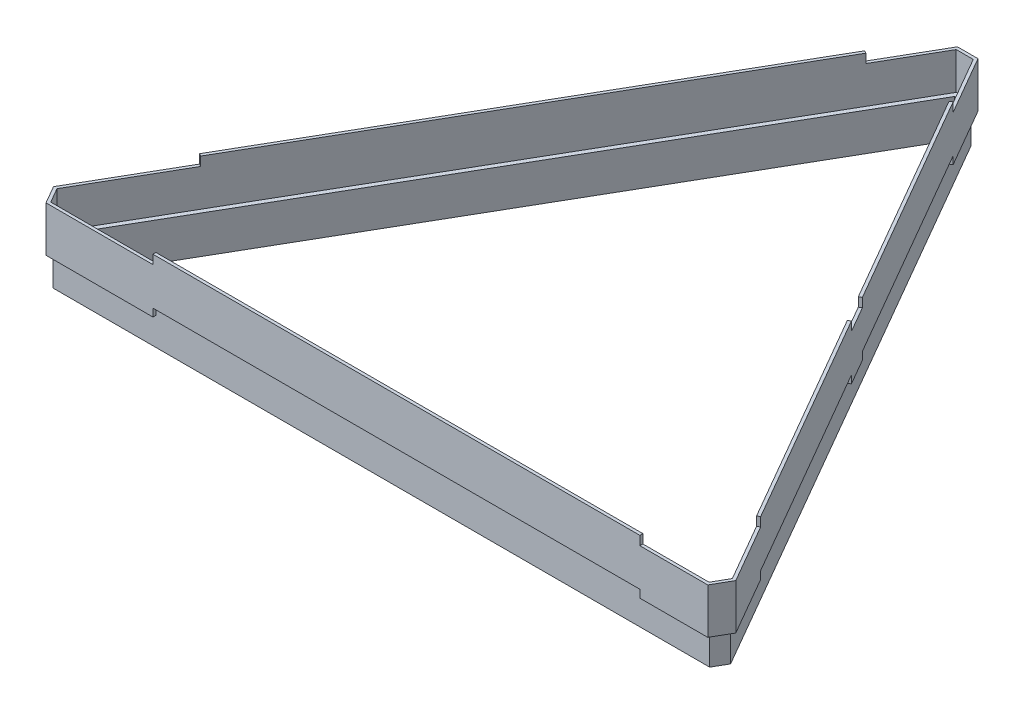
SolidWorks part; units mm, degrees
ref_plane "Front Plane" through (0, 0, 0) normal (0, 0, 1) x (1, 0, 0)
ref_plane "Top Plane" through (0, 0, 0) normal (0, 1, 0) x (1, 0, 0)
ref_plane "Right Plane" through (0, 0, 0) normal (1, 0, 0) x (0, 0, -1)
sketch "Sketch1" plane through (0, 0, 0) normal (0, 1, 0) x (1, 0, 0)
  line L17 (-4, 192.2576) -> (111, -6.9282) construction
  line L24 (4, 192.2576) -> (-111, -6.9282) construction
  line L25 (-115, 0) -> (115, 0) construction
  line L26 (-96.004, 30.9021) -> (-95.1379, 30.4021)
  line L27 (-111.2679, -2.4641) -> (-110.8349, -2.2141) construction
  line L28 (0, 192.2576) -> (0, 185.3294) construction
  line L29 (113, -3.4641) -> (107, 0) construction
  line L30 (59.5, 96.1288) -> (57.7679, 95.1288) construction
  line L31 (-59.5, 96.1288) -> (-57.7679, 95.1288) construction
  line L33 (-112.6906, 0) -> (-109.8453, -4.9282)
  line L36 (112.6906, 0) -> (109.8453, -4.9282)
  line L37 (-2.8453, 190.2576) -> (2.8453, 190.2576)
  line L46 (-74.74, -4.9282) -> (87.75, -4.9282)
  line L50 (-112.6906, 0) -> (-95.1379, 30.4021)
  line L51 (-13.8929, 171.1225) -> (-95.1379, 30.4021)
  line L52 (-14.759, 171.6225) -> (-13.8929, 171.1225)
  line L53 (-14.759, 171.6225) -> (-96.004, 30.9021)
  line L54 (13.8929, 171.1225) -> (14.759, 171.6225)
  line L55 (-109.8453, -4.9282) -> (-74.74, -4.9282)
  line L56 (109.8453, -4.9282) -> (87.75, -4.9282)
  line L57 (-74.74, -5.9282) -> (-74.74, -4.9282)
  line L58 (61.134, 91.2987) -> (56.134, 99.9589)
  line L59 (-2.8453, 190.2576) -> (-13.8929, 171.1225)
  line L60 (61.134, 91.2987) -> (102.509, 19.6351)
  line L61 (102.509, 19.6351) -> (113.8453, 0)
  line L62 (101.6429, 19.1351) -> (102.509, 19.6351)
  line L63 (101.6429, 19.1351) -> (112.6906, 0)
  line L64 (2.8453, 190.2576) -> (13.8929, 171.1225)
  line L65 (113.8453, 0) -> (110.4226, -5.9282)
  line L66 (56.134, 99.9589) -> (14.759, 171.6225)
  line L67 (55.2679, 99.4589) -> (13.8929, 171.1225)
  line L68 (0, -6.9282) -> (-74.74, -6.9282) construction
  line L69 (-14.759, 171.6225) -> (-3.4226, 191.2576)
  line L70 (-58.634, 95.6288) -> (-96.004, 30.9021) construction
  line L71 (-3.4226, 191.2576) -> (3.4226, 191.2576)
  line L72 (60.2679, 90.7987) -> (61.134, 91.2987)
  line L73 (55.2679, 99.4589) -> (56.134, 99.9589)
  line L74 (55.2679, 99.4589) -> (60.2679, 90.7987)
  line L75 (-74.74, -5.9282) -> (87.75, -5.9282)
  line L76 (60.2679, 90.7987) -> (101.6429, 19.1351)
  line L77 (57.7679, 95.1288) -> (57.3349, 94.8788) construction
  line L78 (57.3349, 94.8788) -> (-110.8349, -2.2141) construction
  line L79 (-110.8349, -2.2141) -> (-112.1132, 0)
  line L80 (-112.1132, 0) -> (-2.5566, 189.7576)
  line L81 (-2.5566, 189.7576) -> (2.5566, 189.7576)
  line L82 (2.5566, 189.7576) -> (112.1132, 0)
  line L83 (112.1132, 0) -> (109.5566, -4.4282)
  line L84 (109.5566, -4.4282) -> (-109.5566, -4.4282)
  line L85 (-109.5566, -4.4282) -> (-110.8349, -2.2141)
  line L86 (-57.3349, 94.8788) -> (-56.4689, 94.3788) construction
  line L93 (-56.4689, 94.3788) -> (-1.9793, 188.7576)
  line L94 (-1.9793, 188.7576) -> (1.9793, 188.7576)
  line L95 (1.9793, 188.7576) -> (110.9585, 0)
  line L96 (110.9585, 0) -> (108.9793, -3.4282)
  line L97 (108.9793, -3.4282) -> (-108.9793, -3.4282)
  line L98 (-108.9793, -3.4282) -> (-110.9585, 0)
  line L99 (-110.9585, 0) -> (-56.4689, 94.3788)
  line L100 (-111.2679, -2.4641) -> (-112.134, -2.9641) construction
  line L101 (-112.134, -2.9641) -> (-113.8453, 0)
  line L102 (-113.8453, 0) -> (-96.004, 30.9021)
  line L103 (-112.134, -2.9641) -> (-110.4226, -5.9282)
  line L104 (-110.4226, -5.9282) -> (-74.74, -5.9282)
  line L105 (3.4226, 191.2576) -> (14.759, 171.6225)
  line L106 (110.4226, -5.9282) -> (87.75, -5.9282)
  line L107 (87.75, -5.9282) -> (87.75, -4.9282)
  point P23 (-57.7679, 95.1288)
  point P28 (57.7679, 95.1288)
  point P29 (58.634, 95.6288)
  point P34 (-58.634, 95.6288)
  point P38 (14.759, 171.6225)
  point P41 (-14.759, 171.6225)
  point P44 (102.509, 19.6351)
  point P47 (-96.004, 30.9021)
  point P48 (59.5, 96.1288)
  point P62 (-54.7369, 93.3788)
  dimension "D1" = 8
  dimension "D2" = 8
  dimension "D3" = 8
  dimension "D4" = 230
  dimension "D5" = 230
  dimension "D6" = 230
  dimension "D7" = 74.74
  dimension "D8" = 2
extrude "Boss-Extrude1" add sketch "Sketch1" along normal blind 0.2 contours L59 L37 L64 | L76 L74 L67 L64 L37 L59 L51 L50 L33 L55 L46 L56 L36 L63 L84 L85 L79 L80 L81 L82 L83 | L67 | L74 | L76 | L63 L36 L56 | L46 | L55 L33 L50 | L51 | L85 L84 L83 L82 L81 L80 L79 region at (-54.9485, 0, -101.0123) region at (-95.8396, 0, -30.1869) region at (-54.2572, 0, -100.6132) region at (-8.7814, 0, -181.2614) region at (6.505, 0, 5.4282) region at (35.0135, 0, -135.5407) region at (98.7976, 0, 5.2935) region at (58.201, 0, -95.3788) region at (81.3885, 0, -55.2169) region at (-111.2172, 0, 0.9587)
extrude "Boss-Extrude2" add sketch "Sketch1<7>" along normal blind 12.58 contours L63 L36 L56 | L59 L37 L64 | L55 L33 L50 | L74 region at (-95.8396, 0, -30.1869) region at (-8.7814, 0, -181.2614) region at (98.7976, 0, 5.2935) region at (58.201, 0, -95.3788)
sketch "Sketch1<7>" plane through (0, 0, 0) normal (0, 1, 0) x (1, 0, 0) same geometry as "Sketch1"
extrude "Boss-Extrude3" add sketch "Sketch1<8>" along normal blind 15.58 contours L46 | L51 | L76 | L67 region at (-54.9485, 0, -101.0123) region at (6.505, 0, 5.4282) region at (35.0135, 0, -135.5407) region at (81.3885, 0, -55.2169)
sketch "Sketch1<8>" plane through (0, 0, 0) normal (0, 1, 0) x (1, 0, 0) same geometry as "Sketch1"
extrude "Boss-Extrude4" add sketch "Sketch1<9>" against normal blind 12.38 contours L85 L84 L83 L82 L81 L80 L79 region at (-111.2172, 0, 0.9587)
sketch "Sketch1<9>" plane through (0, 0, 0) normal (0, 1, 0) x (1, 0, 0) same geometry as "Sketch1"
extrude "Boss-Extrude5" add sketch "Sketch1<10>" against normal blind 2.58 contours L74 | L105 L71 L69 L52 L59 L37 L64 L54 | L103 L104 L57 L55 L33 L50 L26 L102 L101 | L107 L106 L65 L61 L62 L63 L36 L56 region at (-95.8396, 0, -30.1869) region at (-8.7814, 0, -181.2614) region at (98.7976, 0, 5.2935) region at (58.201, 0, -95.3788)
sketch "Sketch1<10>" plane through (0, 0, 0) normal (0, 1, 0) x (1, 0, 0) same geometry as "Sketch1"
